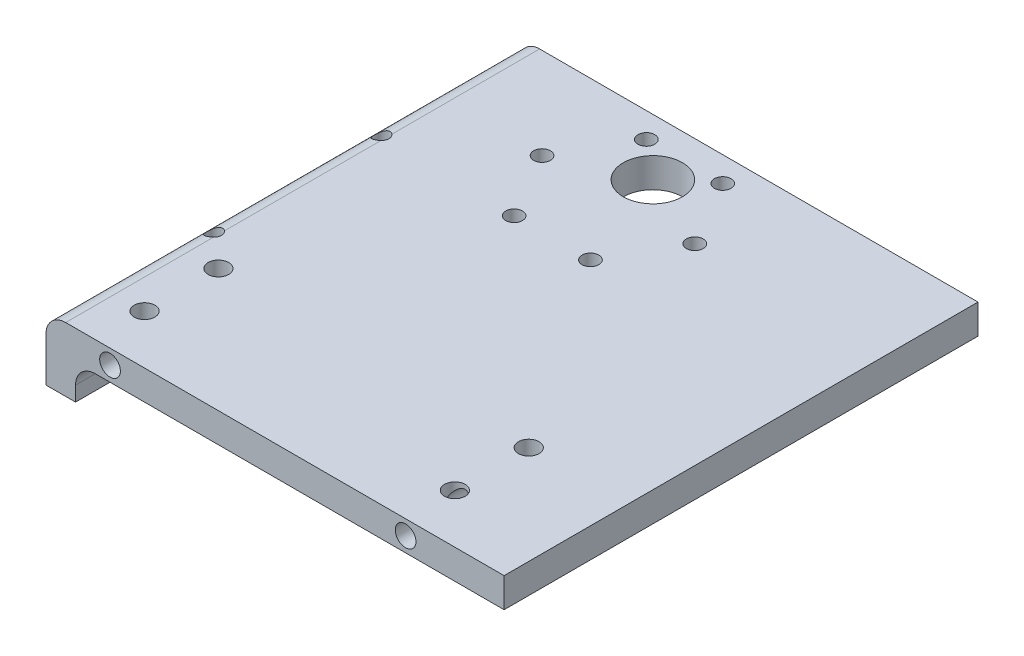
SolidWorks part; units mm, degrees
ref_plane "Front Plane" through (0, 0, 0) normal (1, 0, 0) x (0, 1, 0)
ref_plane "Top Plane" through (0, 0, 0) normal (0, 0, 1) x (0, 1, 0)
ref_plane "Right Plane" through (0, 0, 0) normal (0, 1, 0) x (-1, 0, 0)
sketch "Sketch1" plane through (0, 0, 0) normal (0, 1, 0) x (-1, 0, 0)
  line L0 (-49.4324, 0) -> (-18.4787, 0) construction
  line L1 (0, 0) -> (93, 0)
  line L2 (0, 0) -> (0, 96.2019)
  line L3 (0, 96.2019) -> (93, 96.2019)
  line L4 (93, 0) -> (93, 96.2019)
  line L5 (54.5, -5.8421) -> (54.5, -110.2871) construction
  line L6 (73, -5.0508) -> (73, 63.3751) construction
  line L8 (20, 86.2019) -> (83, 86.2019) construction
  line L9 (20, 86.2019) -> (20, 71.2019) construction
  line L10 (20, 71.2019) -> (83, 71.2019) construction
  line L11 (83, 86.2019) -> (83, 71.2019) construction
  circle A1 centre (54.5, 11.5) radius 6
  circle A2 centre (54.5, 18.5) radius 18.5 construction
  circle A3 centre (54.5, 18.5) radius 15.5 construction
  circle A4 centre (39, 18.5) radius 1.7
  circle A5 centre (46.75, 31.9234) radius 1.7
  circle A6 centre (62.25, 31.9234) radius 1.7
  circle A7 centre (70, 18.5) radius 1.7
  circle A8 centre (62.25, 5.0766) radius 1.7
  circle A9 centre (46.75, 5.0766) radius 1.7
  circle A12 centre (20, 86.2019) radius 2.1
  circle A13 centre (83, 86.2019) radius 2.1
  circle A14 centre (83, 71.2019) radius 2.1
  circle A15 centre (20, 71.2019) radius 2.1
  point P33 (93, 96.2019)
  dimension "D4" = 37
  dimension "D5" = 31
  dimension "D6" = 3.4
  dimension "D7" = 12
  dimension "D11" = 4.2
  dimension "D1" = 96.2019
  dimension "D2" = 93
  dimension "D8" = 7
  dimension "D9" = 20
  dimension "D12" = 10
  dimension "D13" = 20
  dimension "D14" = 10
  dimension "D15" = 15
  dimension "D3" = 6
extrude "Boss-Extrude1" add sketch "Sketch1" along normal blind 6
sketch "Sketch2" plane through (0, 0, 0) normal (0, -1, 0) x (-1, 0, 0)
  line L0 (90, -31.101) -> (90, -65.1009) construction
  line L1 (93, 0) -> (93, -96.2019) construction
  line L2 (93, 0) -> (93, -96.2019)
  line L3 (93, 0) -> (87, 0)
  line L4 (0, 0) -> (93, 0) construction
  line L5 (87, 0) -> (87, -96.2019)
  line L6 (93, -96.2019) -> (0, -96.2019) construction
  line L7 (87, -96.2019) -> (93, -96.2019)
  line L8 (93, -48.1009) -> (87, -48.1009) construction
  circle A0 centre (90, -65.1009) radius 1.5
  circle A1 centre (90, -31.101) radius 1.5
  point P19 (90, -48.1009)
  dimension "D3" = 6
  dimension "D1" = 3
  dimension "D2" = 34
extrude "Boss-Extrude2" add sketch "Sketch2" along normal blind 7
extrude "Cut-Extrude2" cut sketch "Sketch2<3>" against normal through all contours A1 | A0 region at (-90, 0, 65.1009) region at (-90, 0, 31.101)
sketch "Sketch2<3>" plane through (0, 0, 0) normal (0, -1, 0) x (-1, 0, 0) same geometry as "Sketch2"
fillet "Fillet1" radius 4 2 edges at (-87, 0, 48.1009) (-93, 6, 48.1009)
sketch "Sketch3" plane through (0, 0, 0) normal (0, 0, -1) x (1, 0, 0)
  line L0 (-41.5, 0) -> (-41.5, -6) construction
  line L1 (0, 0) -> (-83, 0) construction
  line L2 (0, -6) -> (-89, -6) construction
  line L3 (-80, -3) -> (-20, -3) construction
  line L4 (0, -6) -> (0, 0) construction
  circle A0 centre (-80, -3) radius 2.1
  circle A1 centre (-20, -3) radius 2.1
  point P10 (-41.5, -3)
  dimension "D1" = 20
  dimension "D2" = 4.2
  dimension "D3" = 60
extrude "Cut-Extrude3" cut sketch "Sketch3" against normal blind 18
extrude "Cut-Extrude4" cut sketch "Sketch3<2>" along normal blind 18 from surface starting at face at (-66.7071, -0.2929, 96.2019)
sketch "Sketch3<2>" plane through (0, 0, 0) normal (0, 0, -1) x (1, 0, 0) same geometry as "Sketch3"
equation "\"MotorDriverLength\"= 60mm"
equation "\"MotorLength\"= 60"
equation "\"MotorDriverWidth\"=44"
equation "\"MotorWidth\"= 37"
equation "\"InnerWallThickness\"=3"
equation "\"BatteryWidth\"= 60"
equation "\"OuterWallThickness\" = 6"
equation "\"CompartmentHeight\"=37"
equation "\"CompartmentWidth\"= \"MotorDriverLength\""
equation "\"MotorDiameter\"=37"
equation "\"BatteryHeight\"=24.2019"
equation "\"MotorDriverHeight\"=28"
equation "\"CircuitHeight\"=30"
equation "\"FanThickness\"= 10"
equation "\"FanHeight\"=50"
equation "\"MotorShaftHole\"=12"
equation "\"BearingBore\"=10"
equation "\"MinShinWidth\"= 20"
equation "\"ShinThickness\"=10"
equation "\"PivotDistance\"=30"
equation "\"ThighLength\"= 150"
equation "\"KneeLength\" =80"
equation "\"HipBore\"=27"
equation "\"ThighThickness\"=10"
equation "\"MaxBending\"=135"
equation "\"MaxStretchingAngle\"= 50"
equation "\"ThighJointDistance\"=157.485"
equation "\"ShinLength\"=120"
equation "\"BearingDiameter\"= 10"
equation "\"CircuitLength\"=50"
equation "\"ChessisInnerWidth\"= \"OuterWallThickness\" * 2 + \"MotorDriverLength\" + \"MotorDiameter\" + \"InnerWallThickness\" * 3 + \"CircuitLength\""
equation "\"ChessisHeight\"= \"BatteryHeight\" + 10 + \"InnerWallThickness\" + \"MotorDiameter\" + 10 + \"OuterWallThickness\" * 2"
equation "\"ChassisWidth\"= \"MotorDriverWidth\"*4+30"
equation "\"D1@Sketch1\"=\"ChessisHeight\""
equation "\"D2@Sketch1\"=\"MotorWidth\"+\"FanThickness\"*2 +\"OuterWallThickness\"+30"
equation "\"D9@Sketch1\"=\"FanThickness\"*2"
equation "\"D1@Boss-Extrude1\"=\"OuterWallThickness\""
equation "\"D1@Boss-Extrude2\"=\"OuterWallThickness\"+1"
equation "\"D2@Sketch2\"=17*2"
